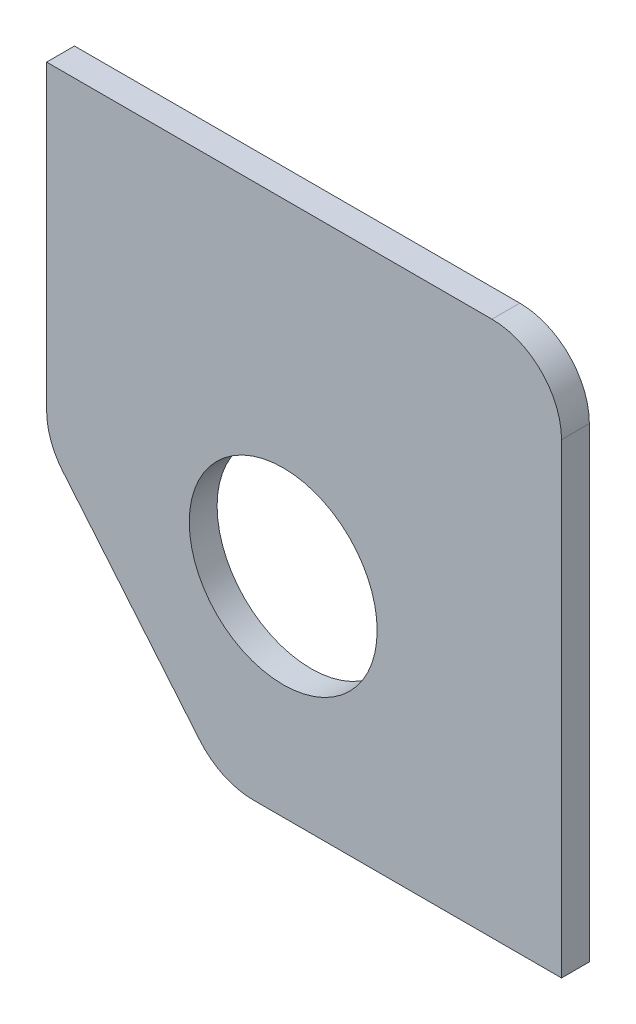
SolidWorks part; units mm, degrees
ref_plane "Plano frontal" through (0, 0, 0) normal (0, 0, 1) x (1, 0, 0)
ref_plane "Plano superior" through (0, 0, 0) normal (0, 1, 0) x (1, 0, 0)
ref_plane "Plano direito" through (0, 0, 0) normal (1, 0, 0) x (0, 0, -1)
sketch "Esboço1" plane through (0, 0, 0) normal (0, 0, 1) x (1, 0, 0)
  line L1 (-86.1657, 44.0263) -> (-12.1657, 44.0263)
  line L2 (-86.1657, 44.0263) -> (-86.1657, -32.9737)
  line L3 (-86.1657, -32.9737) -> (-12.1657, -32.9737)
  line L4 (-12.1657, 44.0263) -> (-12.1657, -32.9737)
  dimension "D1" = 77
  dimension "D2" = 74
extrude "Ressalto-extrusão1" add sketch "Esboço1" along normal blind 4
sketch "Esboço2" plane through (0, 0, 4) normal (0, 0, 1) x (1, 0, 0)
  circle A0 centre (-52.1657, -2.9737) radius 13.5
  dimension "D1" = 27
  dimension "D2" = 34
  dimension "D3" = 30
extrude "Corte-extrusão1" cut sketch "Esboço2" against normal blind 4 and the other way blind 4
sketch "Esboço4" plane through (0, 0, 4) normal (0, 0, 1) x (1, 0, 0)
  line L0 (-61.1657, -32.9737) -> (-86.1657, -2.9737)
  line L1 (-86.1657, -32.9737) -> (-12.1657, -32.9737) construction
  line L2 (-86.1657, 44.0263) -> (-86.1657, -32.9737) construction
  dimension "D1" = 30
  dimension "D2" = 25
extrude "Corte-extrusão2" cut sketch "Esboço4" against normal through all and the other way through all
fillet "Filete2" radius 10 1 edges at (-86.1657, -2.9737, 2) type face fillet first side face at (-86.1657, 20.5263, 2) second side face at (-73.6657, -17.9737, 2)
fillet "Filete3" radius 10 1 edges at (-61.1657, -32.9737, 2) type face fillet first side face at (-72.5068, -19.3644, 2) second side face at (-36.6657, -32.9737, 2)
fillet "Filete4" radius 10 1 edges at (-12.1657, 44.0263, 2) type face fillet first side face at (-49.1657, 44.0263, 2) second side face at (-12.1657, 5.5263, 2)
